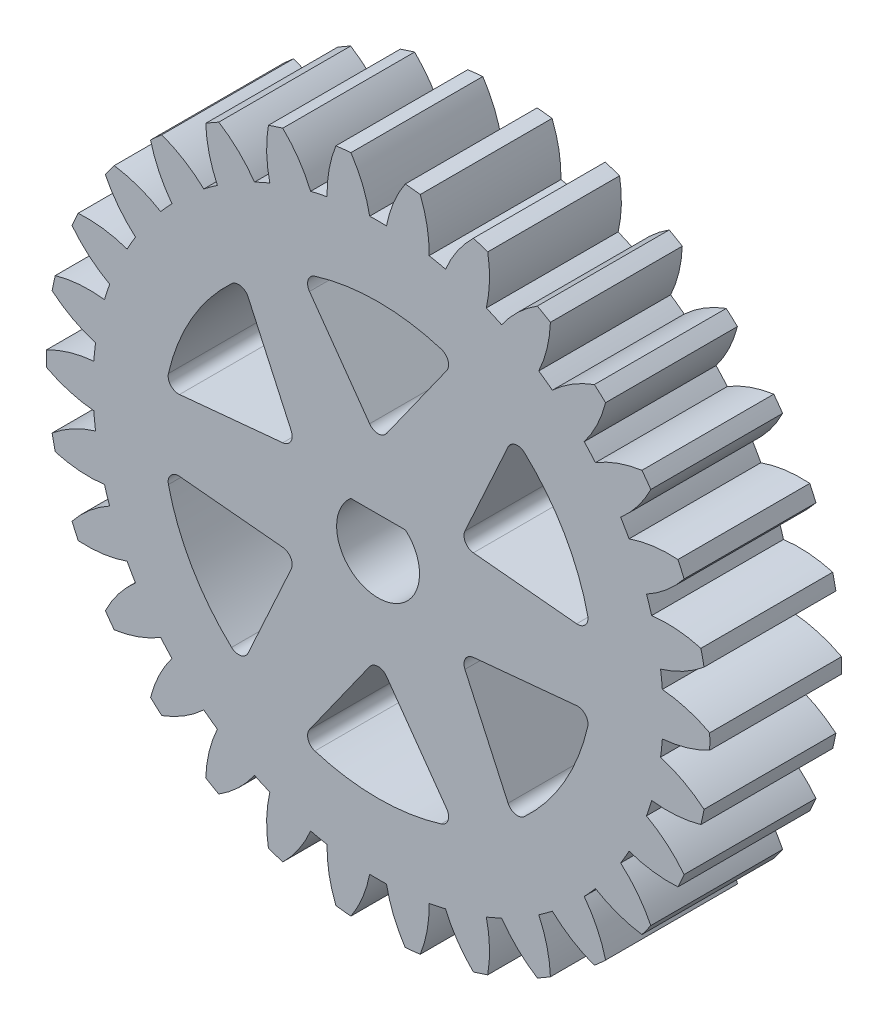
SolidWorks part; units mm, degrees
ref_plane "Front Plane" through (0, 0, 0) normal (0, 0, 1) x (1, 0, 0)
ref_plane "Top Plane" through (0, 0, 0) normal (0, 1, 0) x (1, 0, 0)
ref_plane "Right Plane" through (0, 0, 0) normal (1, 0, 0) x (0, 0, -1)
sketch "Sketch1" plane through (0, 0, 0) normal (0, 0, 1) x (1, 0, 0)
  circle A0 centre (0, 0) radius 16
  dimension "addendumDiameter" = 32
extrude "Boss-Extrude1" add sketch "Sketch1" along normal blind 6.36
sketch "Sketch2" plane through (0, 0, 6.36) normal (0, 0, 1) x (1, 0, 0)
  circle A0 centre (0, 0) radius 15 construction
  circle A1 centre (0, 0) radius 14.0954 construction
  circle A2 centre (0, 0) radius 13.75 construction
  dimension "D1" = 27.5
  dimension "D2" = 28.1908
  dimension "D3" = 30
sketch "Sketch3" plane through (0, 0, 6.36) normal (0, 0, 1) x (1, 0, 0)
  line L0 (0, 0) -> (0, 38.0024) construction
  line L1 (0, 0) -> (-1.5164, 14.4272) construction
  line L2 (-0.7847, 14.9795) -> (-1.5658, 14.8974) construction
  arc A0 (-1.31, 15.9463) -> (-0.4053, 13.744) centre (-6.2972, 12.6105) cw
  circle A1 centre (0, 0) radius 14.0954 construction
  circle A2 centre (0, 0) radius 16 construction
  circle A3 centre (0, 0) radius 13.75 construction
  arc A4 (1.31, 15.9463) -> (0.4053, 13.744) centre (6.2972, 12.6105) ccw
  arc A5 (-1.31, 15.9463) -> (1.31, 15.9463) centre (0, 0) cw
  arc A6 (0.4053, 13.744) -> (-0.4053, 13.744) centre (0, 0) ccw
  circle A7 centre (0, 0) radius 15 construction
  dimension "D2" = 6
  dimension "D1" = 6
  dimension "D3" = 0.7854
extrude "Cut-Extrude1" cut sketch "Sketch3" against normal through all
ref_axis "Axis2" through (0, 0, 6.36) along (0, 0, -1)
pattern_circular "CirPattern1" count 30 over 360 about axis through (0, 0, 6.36) along (0, 0, -1) of "Cut-Extrude1"
sketch "Sketch6" plane through (0, 0, 0) normal (0, 0, -1) x (-1, 0, 0)
  line L2 (1.3229, 1.5) -> (-1.3229, 1.5)
  arc A8 (-1.3229, 1.5) -> (1.3229, 1.5) centre (0, 0) ccw
  dimension "D1" = 1.5
  dimension "D2" = 4
extrude "Cut-Extrude4" cut sketch "Sketch6" against normal through all
sketch "Sketch7" plane through (0, 0, 0) normal (0, 0, -1) x (-1, 0, 0)
  line L0 (0, 4.5) -> (3.6957, 9.6944)
  line L1 (0, 4.5) -> (-3.6957, 9.6944)
  arc A0 (3.6957, 9.6944) -> (-3.6957, 9.6944) centre (0, 0) ccw
  point P6 (0, 10.375)
  dimension "D1" = 10.375
  dimension "D2" = 6.375
  dimension "D3" = 4.5
extrude "Cut-Extrude5" cut sketch "Sketch7" against normal through all
fillet "Fillet3" radius 0.5 3 edges at (0, 4.5, 3.18) (-3.6957, 9.6944, 3.18) (3.6957, 9.6944, 3.18)
ref_axis "Axis3" through (0, 0, 0) along (0, 0, 1)
pattern_circular "CirPattern2" count 6 over 360 about axis through (0, 0, 0) along (0, 0, 1) of "Cut-Extrude5", "Fillet3"
equation "\"module\" = 1.0"
equation "\"teeth\"= 30"
equation "\"pressureAngle\"= 20deg"
equation "\"gearThickness\"=6.36"
equation "\"addendumFactor\"= 1"
equation "\"dedendumFactor\"= 1.25"
equation "\"pitch\"= 1 / \"module\""
equation "\"pitchDiameter\"= \"teeth\" / \"pitch\""
equation "\"addendum\"= \"addendumFactor\" / \"pitch\""
equation "\"dedendum\"= \"dedendumFactor\" / \"pitch\""
equation "\"D1@Boss-Extrude1\"=\"gearThickness\""
equation "\"D1@Sketch2\"=\"pitchDiameter\" - 2* \"dedendum\""
equation "\"D2@Sketch2\"=\"pitchDiameter\" * cos(\"pressureAngle\")"
equation "\"D3@Sketch2\"=\"pitchDiameter\""
equation "\"D1@Sketch3\"=180/\"teeth\""
equation "\"D2@Sketch3\"=\"pitchDiameter\"/5"
equation "\"D3@Sketch3\"=PI/2/\"pitch\"/2"
equation "\"D1@CirPattern1\"=\"teeth\""
equation "\"addendumDiameter@Sketch1\"=\"pitchDiameter\" + 2* \"addendum\""
equation "\"D2@CirPattern1\"=360/\"teeth\""
equation "\"D2@Sketch7\"=\"D1@Sketch7\"-4"
equation "\"D1@Sketch7\"=(\"pitchDiameter\"-\"dedendum\")/2-4"
